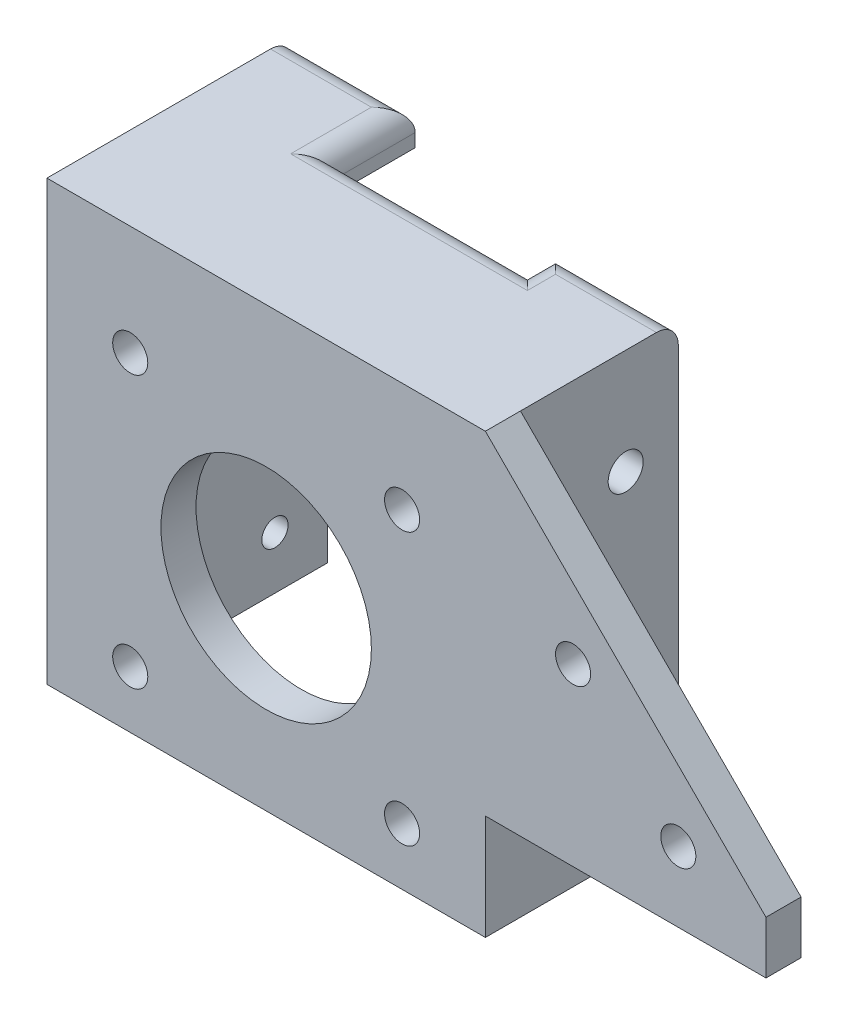
SolidWorks part; units mm, degrees
ref_plane "Front Plane" through (0, 0, 0) normal (0, 0, 1) x (1, 0, 0)
ref_plane "Top Plane" through (0, 0, 0) normal (0, 1, 0) x (1, 0, 0)
ref_plane "Right Plane" through (0, 0, 0) normal (1, 0, 0) x (0, 0, -1)
sketch "Sketch1" plane through (0, 0, 0) normal (0, 0, 1) x (1, 0, 0)
  line L0 (-50.3416, 0) -> (46.1674, 0) construction
  line L1 (0, -28.4394) -> (0, 79.8206) construction
  line L2 (57, 18) -> (25, 50)
  line L4 (-25, 0) -> (-25, 50)
  line L5 (-25, 50) -> (25, 50)
  line L6 (57, 12) -> (57, 18)
  line L7 (25, -2.2452) -> (25, 66.7313) construction
  line L10 (57, 12) -> (25, 12)
  line L11 (25, 12) -> (25, 0)
  line L12 (25, 0) -> (-25, 0)
  dimension "D1" = 50
  dimension "D2" = 38
  dimension "D3" = 6
  dimension "D5" = 25
  dimension "D6" = 45
  dimension "D7" = 50
extrude "Boss-Extrude1" add sketch "Sketch1" along normal blind 4
sketch "Sketch2" plane through (0, 0, 4) normal (0, 0, 1) x (1, 0, 0)
  line L0 (-39.1184, 22) -> (53, 22) construction
  line L1 (0, -8.7046) -> (0, 47.1631) construction
  line L2 (57, 18) -> (25, 50) construction
  line L3 (-15.5, 6.5) -> (15.5, 6.5) construction
  line L4 (-15.5, 6.5) -> (-15.5, 37.5) construction
  line L5 (-15.5, 37.5) -> (15.5, 37.5) construction
  line L6 (15.5, 6.5) -> (15.5, 37.5) construction
  line L7 (-15.5, 6.5) -> (15.5, 37.5) construction
  line L8 (-15.5, 37.5) -> (15.5, 6.5) construction
  line L9 (-25, 0) -> (25, 0) construction
  circle A0 centre (0, 22) radius 12
  circle A1 centre (15.5, 6.5) radius 2
  circle A2 centre (15.5, 37.5) radius 2
  circle A3 centre (-15.5, 37.5) radius 2
  circle A4 centre (-15.5, 6.5) radius 2
  point P4 (0, 22)
  dimension "D1" = 4
  dimension "D4" = 24
  dimension "D2" = 31
  dimension "D3" = 22
extrude "Cut-Extrude1" cut sketch "Sketch2" against normal through all
sketch "Sketch9" plane through (0, 0, 0) normal (0, 0, -1) x (-1, 0, 0)
  line L0 (-61, 20) -> (-35, 20) construction
  line L1 (-35, 20) -> (-35, 48.0747) construction
  line L2 (-25, -5.4794) -> (-25, 53.2688) construction
  line L3 (-25, 12) -> (-57, 12) construction
  circle A1 centre (-47, 20) radius 2
  circle A2 centre (-35, 32) radius 2
  dimension "D2" = 10
  dimension "D5" = 4
  dimension "D1" = 12
  dimension "D3" = 12
  dimension "D4" = 8
extrude "Cut-Extrude2" cut sketch "Sketch9" against normal blind 4
sketch "Sketch13" plane through (0, 0, 4) normal (0, 0, 1) x (1, 0, 0)
  line L8 (-25, 34.0255) -> (-45, 34.0255)
  line L9 (-25, 50) -> (-25, 0) construction
  line L10 (-45, 34.0255) -> (-45, 96.6007)
  line L11 (-45, 96.6007) -> (-32.0913, 96.6007)
  line L13 (57, 18) -> (25, 50) construction
  line L14 (25, 50) -> (19, 56)
  line L15 (-25, 34.0255) -> (-25, 50)
  line L17 (-32.0913, 96.6007) -> (-32.0913, 74.4017)
  line L20 (19, 56) -> (-3.8448, 56)
  line L21 (25, 50) -> (-25, 50)
  arc A3 (-3.8448, 56) -> (-32.0913, 74.4017) centre (-11.974, 74.4017) cw
  dimension "D1" = 20
  dimension "D2" = 6
extrude "Boss-Extrude7" [suppressed] add sketch "Sketch13" against normal blind 4
sketch "Sketch16" [suppressed] plane through (0, 0, 4) normal (0, 0, 1) x (1, 0, 0)
  line L0 (-38.5457, 92.6569) -> (2.0281, 52.0832) construction
  line L1 (-45, 34.0255) -> (-25, 34.0255) construction
  line L2 (-38.5457, 96.6007) -> (-38.5457, 85.5222) construction
  line L3 (-32.0913, 96.6007) -> (-45, 96.6007) construction
  circle A0 centre (2.0281, 52.0832) radius 2
  circle A1 centre (-38.5457, 92.6569) radius 2
  dimension "D3" = 4
  dimension "D1" = 57.38
  dimension "D2" = 45
extrude "Cut-Extrude6" [suppressed] cut sketch "Sketch16" against normal blind 4
sketch "Sketch17" plane through (0, 0, 0) normal (0, 0, -1) x (-1, 0, 0)
  line L0 (-25, 0) -> (-25, 50)
  line L2 (-25, 50) -> (25, 50)
  line L3 (25, 50) -> (25, 0) construction
  line L4 (25, 50) -> (25, 0)
  line L5 (25, 0) -> (21, 0)
  line L6 (25, 0) -> (-25, 0) construction
  line L7 (21, 0) -> (21, 46)
  line L8 (21, 46) -> (-21, 46)
  line L9 (-21, 46) -> (-21, 0)
  line L10 (-21, 0) -> (-25, 0)
  dimension "D1" = 42
  dimension "D2" = 21
  dimension "D3" = 4
extrude "Boss-Extrude8" add sketch "Sketch17" along normal blind 24
sketch "Sketch18" plane through (25, 0, 0) normal (1, 0, 0) x (0, 0, -1)
  line L0 (12, 4.8734) -> (12, 63.3892) construction
  circle A0 centre (12, 38) radius 2
  circle A1 centre (12, 20) radius 2
  dimension "D1" = 4
  dimension "D2" = 20
  dimension "D3" = 18
  dimension "D4" = 12
extrude "Cut-Extrude7" cut sketch "Sketch18" against normal up to surface (4 mm away) up to face at (21, 23, -12)
sketch "Sketch19" plane through (-25, 0, 0) normal (-1, 0, 0) x (0, 0, 1)
  line L0 (-6, 10) -> (-6, 45) construction
  line L2 (4, 0) -> (-24, 0) construction
  line L4 (-18, 6) -> (-6, 6) construction
  line L5 (-18, 6) -> (-18, 41) construction
  line L6 (-18, 41) -> (-6, 41) construction
  line L7 (-6, 6) -> (-6, 41) construction
  circle A0 centre (-18, 6) radius 1.5
  circle A2 centre (-18, 41) radius 1.5
  circle A5 centre (-6, 10) radius 1.5
  circle A6 centre (-6, 45) radius 1.5
  point P14 (-4, 9.1146)
  dimension "D5" = 3
  dimension "D7" = 10
  dimension "D1" = 6
  dimension "D2" = 6
  dimension "D3" = 35
  dimension "D4" = 12
  dimension "D6" = 35
extrude "Cut-Extrude8" cut sketch "Sketch19" against normal blind 10
sketch "Sketch20" plane through (0, 50, 0) normal (0, 1, 0) x (1, 0, 0)
  line L0 (-25, 24) -> (25, 24) construction
  line L1 (25, 24) -> (-11, 24)
  line L2 (25, 24) -> (25, 18)
  line L4 (-11, 24) -> (-11, 14.7918)
  line L6 (25, 24) -> (25, 0) construction
  line L7 (-11, 14.7918) -> (11, 14.7918)
  line L8 (11, 14.7918) -> (11, 18)
  line L9 (11, 18) -> (25, 18)
  dimension "D1" = 22
  dimension "D2" = 6
  dimension "D3" = 14
extrude "Cut-Extrude9" cut sketch "Sketch20" against normal up to surface (50 mm away) up to face at (0, 0, -11)
fillet "Fillet1" radius 2.5 5 edges at (18, 50, -18) (11, 50, -16.3959) (-11, 50, -19.3959) (0, 50, -14.7918) (-18, 50, -24)
equation "\"motor_plate_thickness\"=4"
equation "\"D1@Boss-Extrude1\"=\"motor_plate_thickness\""
equation "\"motor_hub_diameter\"=24"
equation "\"D4@Sketch2\"=\"motor_hub_diameter\""
equation "\"motor_mount_hole_od\"=4"
equation "\"D1@Sketch2\"=\"motor_mount_hole_od\""
equation "\"motor_mount_hole_spacing\"=31"
equation "\"D2@Sketch2\"=\"motor_mount_hole_spacing\""
